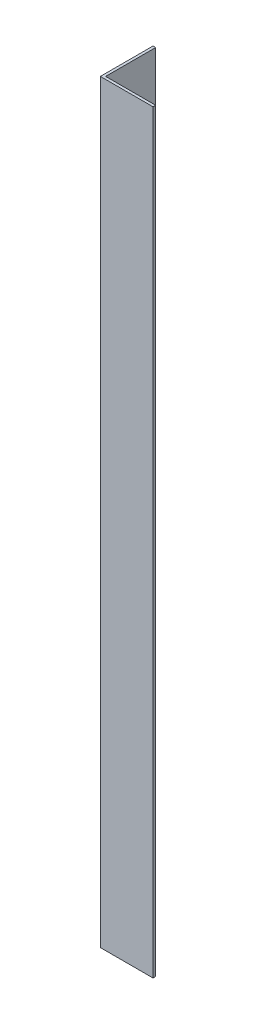
SolidWorks part; units mm, degrees
material "1060 Сплав"
ref_plane "Спереди" through (0, 0, 0) normal (0, 0, 1) x (1, 0, 0)
ref_plane "Сверху" through (0, 0, 0) normal (0, 1, 0) x (1, 0, 0)
ref_plane "Справа" through (0, 0, 0) normal (1, 0, 0) x (0, 0, -1)
sketch "Эскиз1" plane through (0, 0, 0) normal (0, 1, 0) x (1, 0, 0)
  line L0 (0, 0) -> (0, 15)
  line L1 (0, 15) -> (0.75, 15)
  line L2 (0.75, 15) -> (0.75, 0.75)
  line L3 (0.75, 0.75) -> (15, 0.75)
  line L4 (15, 0.75) -> (15, 0)
  line L5 (15, 0) -> (0, 0)
  dimension "D1" = 0.75
  dimension "D2" = 15
extrude "Бобышка-Вытянуть1" add sketch "Эскиз1" along normal blind 215
